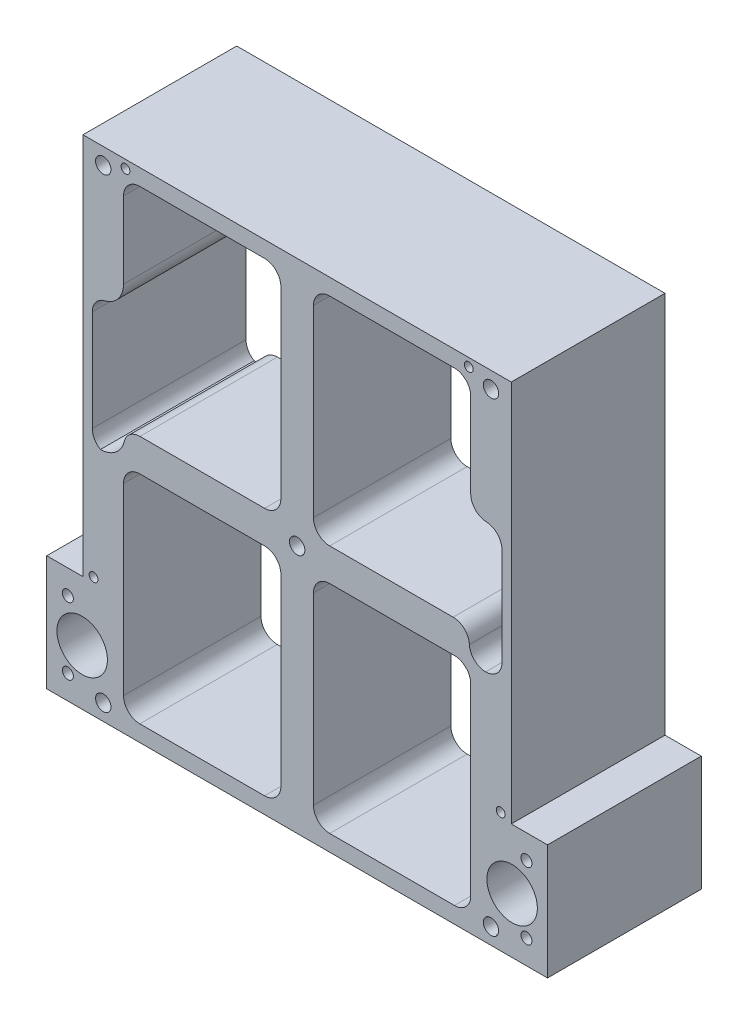
SolidWorks part; units mm, degrees
ref_plane "Front Plane" through (0, 0, 0) normal (0, 0, 1) x (1, 0, 0)
ref_plane "Top Plane" through (0, 0, 0) normal (0, 1, 0) x (1, 0, 0)
ref_plane "Right Plane" through (0, 0, 0) normal (1, 0, 0) x (0, 0, -1)
sketch "Sketch1" plane through (0, 0, 0) normal (0, 0, 1) x (1, 0, 0)
  line L0 (-85.5662, 44.958) -> (-97.6313, 44.958) construction
  line L1 (-97.6313, 44.958) -> (-97.6313, 0) construction
  line L2 (-97.6313, 0) -> (97.6313, 0) construction
  line L3 (97.6313, 0) -> (97.6312, 44.958) construction
  line L4 (97.6312, 44.958) -> (85.5663, 44.958) construction
  line L8 (83.5025, 45.5422) -> (83.5025, 194.183) construction
  line L9 (83.5025, 194.183) -> (-83.5025, 194.183) construction
  line L10 (-83.5025, 194.183) -> (-83.5025, 45.5422) construction
  line L14 (-83.5025, 44.958) -> (-97.6313, 44.958)
  line L15 (-97.6313, 44.958) -> (-97.6313, 0)
  line L16 (-97.6313, 0) -> (97.6313, 0)
  line L17 (97.6313, 0) -> (97.6312, 44.958)
  line L18 (97.6312, 44.958) -> (83.5025, 44.958)
  line L22 (83.5025, 44.958) -> (83.5025, 194.183)
  line L23 (83.5025, 194.183) -> (-83.5025, 194.183)
  line L24 (-83.5025, 194.183) -> (-83.5025, 44.958)
extrude "Boss-Extrude1" add sketch "Sketch1" against normal blind 59.944
sketch "Sketch2" plane through (0, 0, -59.944) normal (0, 0, -1) x (-1, 0, 0)
  line L0 (-38.54, -49.697) -> (-38.54, -49.707)
  line L1 (-38.54, -49.707) -> (74.04, -49.707)
  line L2 (74.04, -49.707) -> (74.04, 190.373)
  line L3 (74.04, 190.373) -> (-74.04, 190.373)
  line L4 (-74.04, 190.373) -> (-74.04, -49.707)
  line L5 (-74.04, -49.707) -> (-43.46, -49.707)
  line L6 (-43.46, -49.707) -> (-43.46, -49.697)
  line L7 (-43.46, -49.697) -> (-38.54, -49.697)
  line L8 (-36, -47.157) -> (-36, -47.167)
  line L9 (-36, -47.167) -> (71.5, -47.167)
  line L10 (71.5, -47.167) -> (71.5, 187.833)
  line L11 (71.5, 187.833) -> (-71.5, 187.833)
  line L12 (-71.5, 187.833) -> (-71.5, -47.167)
  line L13 (-71.5, -47.167) -> (-46, -47.167)
  line L14 (-46, -47.167) -> (-46, -47.157)
  line L15 (-46, -47.157) -> (-36, -47.157)
  line L16 (-36, -47.157) -> (-36, -47.167) construction
  line L17 (-36, -47.167) -> (71.5, -47.167) construction
  line L18 (71.5, -47.167) -> (71.5, 187.833) construction
  line L19 (71.5, 187.833) -> (-71.5, 187.833) construction
  line L20 (-71.5, 187.833) -> (-71.5, -47.167) construction
  line L21 (-71.5, -47.167) -> (-46, -47.167) construction
  line L22 (-46, -47.167) -> (-46, -47.157) construction
  line L23 (-46, -47.157) -> (-36, -47.157) construction
  dimension "D1" = 0
  dimension "D2" = 2.54
extrude "Cut-Extrude1" cut sketch "Sketch2" against normal blind 6.35
sketch "Sketch3" plane through (0, 0, -59.944) normal (0, 0, -1) x (-1, 0, 0)
  line L0 (-71.49, 45.353) -> (-71.49, 83.653) construction
  line L1 (-71.5, 64.5639) -> (-78.8025, 64.5639) construction
  line L2 (-71.5, 187.833) -> (-71.5, -47.167) construction
  line L3 (-74.04, 190.373) -> (-74.04, 0) construction
  line L4 (-71.5, 86.1539) -> (-78.8025, 86.1539)
  line L5 (-71.5, 42.9739) -> (-78.8025, 42.9739)
  line L6 (-71.5, 86.1539) -> (-71.5, 42.9739)
  line L7 (-78.8025, 86.1539) -> (-78.8025, 42.9739)
  dimension "D1" = 4.7625
  dimension "D2" = 21.59
  dimension "D3" = 21.59
extrude "Cut-Extrude2" cut sketch "Sketch3" against normal up to surface (6.35 mm away) up to face at (0, 95.1865, -53.594)
sketch "Sketch4" plane through (0, 0, -59.944) normal (0, 0, -1) x (-1, 0, 0)
  arc A0 (93.4715, 23.5197) -> (93.4715, 19.6603) centre (83.82, 21.59) ccw construction
  arc A1 (-74.1685, 23.5197) -> (-74.1685, 19.6603) centre (-83.82, 21.59) ccw construction
  circle A2 centre (83.82, 21.59) radius 9.8425
  circle A3 centre (-83.82, 21.59) radius 9.8425
extrude "Cut-Extrude3" cut sketch "Sketch4" against normal through all
hole_wizard "Hole1" positions "Sketch6" profile "Sketch5" legacy
sketch "Sketch6" plane through (0, 0, -59.944) normal (0, 0, -1) x (-1, 0, 0)
  line L0 (-97.6313, 22.479) -> (97.6313, 22.479) construction
  line L4 (-97.6313, 0) -> (-97.6312, 44.958) construction
  line L5 (97.6313, 44.958) -> (97.6313, 0) construction
  point P0 (-89.408, 35.56)
  point P3 (89.408, 35.56)
  point P16 (-89.408, 9.398)
  point P17 (89.408, 9.398)
sketch "Sketch5" plane through (89.408, 35.56, -59.944) normal (1, 0, 0) x (0, 1, 0)
  line L0 (0, 0) -> (0, 3.81)
  line L1 (0, 3.81) -> (2.5273, 3.81)
  line L2 (2.5273, 3.81) -> (2.6543, 0)
  line L3 (2.6543, 0) -> (0, 0)
  line L4 (0, 110) -> (0, -10) construction
  dimension "Minor Diameter" = 5.0546
  dimension "Depth" = 3.81
  dimension "Major Diameter" = 5.3086
hole_wizard "#6 Clearance Hole1" positions "Sketch8" profile "Sketch9" hole size "#6" standard "ANSI Inch" end condition through all
sketch "Sketch8" plane through (0, 0, -59.944) normal (0, 0, -1) x (-1, 0, 0)
  line L0 (-97.6312, 22.479) -> (97.6313, 22.479) construction
  line L1 (-97.6313, 0) -> (-97.6312, 44.958) construction
  line L2 (97.6313, 44.958) -> (97.6313, 0) construction
  point P0 (-89.408, 35.56)
  point P3 (89.408, 35.56)
  point P13 (89.408, 9.398)
  point P14 (-89.408, 9.398)
sketch "Sketch9" plane through (89.408, 35.56, -59.944) normal (1, 0, 0) x (0, 1, 0)
  line L0 (0, 0) -> (0, 59.944)
  line L1 (0, 59.944) -> (2.1526, 59.944)
  line L2 (2.1526, 59.944) -> (2.1526, 0)
  line L5 (2.1526, 0) -> (0, 0)
  line L11 (0, -6.35) -> (0, 107.95) construction
  dimension "Thru Hole Dia." = 4.3053
  dimension "Thru Hole Depth" = 59.944
sketch "Sketch10" plane through (0, 0, -59.944) normal (0, 0, -1) x (-1, 0, 0)
  circle A0 centre (-79.375, 46.863) radius 3.175
  circle A1 centre (-66.929, 191.008) radius 3.175
  circle A2 centre (66.929, 191.008) radius 3.175
  circle A3 centre (79.375, 46.863) radius 3.175
  dimension "D1" = 6.35
extrude "Boss-Extrude2" add sketch "Sketch10" against normal up to next (59.944 mm away)
hole_wizard "Hole2" positions "Sketch12" profile "Sketch11" legacy
sketch "Sketch12" plane through (0, 0, -59.944) normal (0, 0, -1) x (-1, 0, 0)
  point P0 (66.929, 191.008)
  point P2 (-66.929, 191.008)
  point P4 (-79.375, 46.863)
  point P6 (79.375, 46.863)
sketch "Sketch11" plane through (-66.929, 191.008, -59.944) normal (1, 0, 0) x (0, 1, 0)
  line L0 (0, 0) -> (0, 3.429)
  line L1 (0, 3.429) -> (1.9431, 3.429)
  line L2 (1.9431, 3.429) -> (2.0701, 0)
  line L3 (2.0701, 0) -> (0, 0)
  line L4 (0, 110) -> (0, -10) construction
  dimension "Minor Diameter" = 3.8862
  dimension "Depth" = 3.429
  dimension "Major Diameter" = 4.1402
hole_wizard "#4 Clearance Hole1" positions "Sketch14" profile "Sketch13" hole size "#4" standard "ANSI Inch" end condition through all
sketch "Sketch14" plane through (0, 0, -56.515) normal (0, 0, -1) x (-1, 0, 0)
  point P0 (79.375, 46.863)
  point P2 (-79.375, 46.863)
  point P5 (-66.929, 191.008)
  point P7 (66.929, 191.008)
sketch "Sketch13" plane through (-79.375, 46.863, -56.515) normal (1, 0, 0) x (0, 1, 0)
  line L0 (0, 0) -> (0, 56.515)
  line L1 (0, 56.515) -> (1.7272, 56.515)
  line L2 (1.7272, 56.515) -> (1.7272, 0)
  line L5 (1.7272, 0) -> (0, 0)
  line L11 (0, -6.35) -> (0, 107.95) construction
  dimension "Thru Hole Dia." = 3.4544
  dimension "Thru Hole Depth" = 56.515
sketch "Sketch15" plane through (0, 0, -59.944) normal (0, 0, -1) x (-1, 0, 0)
  line L0 (-74.04, 20.4826) -> (-74.04, 0) construction
  line L1 (-83.82, 31.4325) -> (-74.04, 31.4325)
  line L2 (-83.82, 31.4325) -> (-83.82, 11.7475)
  line L3 (-83.82, 11.7475) -> (-74.04, 11.7475)
  line L4 (-74.04, 31.4325) -> (-74.04, 11.7475)
  line L5 (74.04, 190.373) -> (74.04, 22.6974) construction
  line L6 (83.82, 11.7475) -> (74.04, 11.7475)
  line L7 (83.82, 11.7475) -> (83.82, 31.4325)
  line L8 (83.82, 31.4325) -> (74.04, 31.4325)
  line L9 (74.04, 11.7475) -> (74.04, 31.4325)
  arc A0 (-74.04, 22.6974) -> (-74.04, 20.4826) centre (-83.82, 21.59) ccw construction
  arc A1 (74.04, 20.4826) -> (74.04, 22.6974) centre (83.82, 21.59) ccw construction
  point P0 (-83.82, 21.59)
  point P11 (83.82, 21.59)
extrude "Cut-Extrude4" cut sketch "Sketch15" against normal up to surface (6.35 mm away) up to face at (25.5938, 87.5277, -53.594)
chamfer "Chamfer1" distance 2.54 angle 45 4 edges at (-74.04, 11.7475, -56.769) (-74.04, 31.4325, -56.769) (74.04, 11.7475, -56.769) (74.04, 31.4325, -56.769)
sketch "Sketch16" plane through (0, 0, -53.594) normal (0, 0, -1) x (-1, 0, 0)
  line L0 (0, 194.183) -> (0, 0) construction
  line L1 (-83.5025, 194.183) -> (83.5025, 194.183) construction
  line L2 (-74.04, 0) -> (74.04, 0) construction
  line L3 (0, 97.0915) -> (74.04, 97.0915) construction
  line L4 (74.04, 190.373) -> (74.04, 33.9725) construction
  line L5 (74.04, 97.0915) -> (74.04, 0) construction
  line L6 (74.04, 0) -> (0, 0) construction
  line L7 (0, 97.0915) -> (0, 0) construction
  line L8 (6.35, 90.7415) -> (67.69, 90.7415)
  line L9 (67.69, 90.7415) -> (67.69, 6.35)
  line L10 (67.69, 6.35) -> (6.35, 6.35)
  line L11 (6.35, 90.7415) -> (6.35, 6.35)
  line L12 (6.35, 103.4415) -> (6.35, 187.833)
  line L13 (67.69, 187.833) -> (6.35, 187.833)
  line L14 (67.69, 103.4415) -> (67.69, 187.833)
  line L15 (6.35, 103.4415) -> (67.69, 103.4415)
  line L16 (-6.35, 103.4415) -> (-67.69, 103.4415)
  line L17 (-67.69, 103.4415) -> (-67.69, 187.833)
  line L18 (-67.69, 187.833) -> (-6.35, 187.833)
  line L19 (-6.35, 103.4415) -> (-6.35, 187.833)
  line L20 (-6.35, 90.7415) -> (-6.35, 6.35)
  line L21 (-67.69, 6.35) -> (-6.35, 6.35)
  line L22 (-67.69, 90.7415) -> (-67.69, 6.35)
  line L23 (-6.35, 90.7415) -> (-67.69, 90.7415)
  dimension "D1" = 6.35
extrude "Cut-Extrude5" cut sketch "Sketch16" against normal through all
fillet "Fillet1" radius 6.35 16 edges at (6.35, 6.35, -26.797) (6.35, 90.7415, -26.797) (67.69, 90.7415, -26.797) (67.69, 6.35, -26.797) (-6.35, 6.35, -26.797) (-6.35, 90.7415, -26.797) (-67.69, 90.7415, -26.797) (-67.69, 6.35, -26.797) (-67.69, 103.4415, -26.797) (-67.69, 187.833, -26.797) (-6.35, 187.833, -26.797) (-6.35, 103.4415, -26.797) (67.69, 103.4415, -26.797) (6.35, 103.4415, -26.797) (6.35, 187.833, -26.797) (67.69, 187.833, -26.797)
hole_wizard "Hole3" positions "Sketch20" profile "Sketch19" legacy
sketch "Sketch20" plane through (0, 0, 0) normal (0, 0, 1) x (1, 0, 0)
  line L0 (-8.2099, 88.8816) -> (8.2099, 105.3014) construction
  line L3 (75.5963, 6.35) -> (-75.5962, 6.35)
  line L4 (75.5963, 6.35) -> (75.5963, 187.833)
  line L5 (75.5963, 187.833) -> (-75.5962, 187.833)
  line L6 (-75.5962, 6.35) -> (-75.5962, 187.833)
  line L7 (75.5963, 6.35) -> (-75.5962, 187.833) construction
  line L8 (75.5963, 187.833) -> (-75.5962, 6.35) construction
  line L15 (-67.69, 145.6373) -> (-83.5025, 145.6373) construction
  line L16 (-67.69, 109.7915) -> (-67.69, 181.483) construction
  line L17 (-83.5025, 194.183) -> (-83.5025, 44.958) construction
  line L18 (-61.34, 187.833) -> (-12.7, 187.833) construction
  arc A0 (-6.35, 84.3915) -> (-12.7, 90.7415) centre (-12.7, 84.3915) ccw construction
  arc A1 (6.35, 109.7915) -> (12.7, 103.4415) centre (12.7, 109.7915) ccw construction
  point P10 (0, 97.0915)
  point P11 (-75.5962, 187.833)
  point P14 (75.5963, 6.35)
  point P15 (75.5963, 187.833)
  point P16 (-75.5962, 6.35)
  point P108 (-75.5962, 97.0915)
  point P109 (-75.5962, 145.6373)
sketch "Sketch19" plane through (0, 97.0915, 0) normal (1, 0, 0) x (0, -1, 0)
  line L0 (0, 0) -> (0, 4.699)
  line L1 (0, 4.699) -> (2.8702, 4.699)
  line L2 (2.8702, 4.699) -> (2.9972, 0)
  line L3 (2.9972, 0) -> (0, 0)
  line L4 (0, 110) -> (0, -10) construction
  dimension "Minor Diameter" = 5.7404
  dimension "Depth" = 4.699
  dimension "Major Diameter" = 5.9944
hole_wizard "#8 Clearance Hole1" positions "Sketch22" profile "Sketch21" hole size "#8" standard "ANSI Inch" end condition through all
sketch "Sketch22" plane through (0, 0, -4.699) normal (0, 0, 1) x (1, 0, 0)
  point P0 (-75.5962, 187.833)
  point P3 (75.5963, 187.833)
  point P6 (75.5963, 6.35)
  point P9 (-75.5962, 6.35)
sketch "Sketch21" plane through (-75.5962, 187.833, -4.699) normal (1, 0, 0) x (0, -1, 0)
  line L0 (0, 0) -> (0, 55.245)
  line L1 (0, 55.245) -> (2.4574, 55.245)
  line L2 (2.4574, 55.245) -> (2.4574, 0)
  line L5 (2.4574, 0) -> (0, 0)
  line L11 (0, -6.35) -> (0, 107.95) construction
  dimension "Thru Hole Dia." = 4.9149
  dimension "Thru Hole Depth" = 55.245
sketch "Sketch23" plane through (0, 0, -59.944) normal (0, 0, -1) x (-1, 0, 0)
  line L0 (-79.8735, 116.713) -> (-67.1735, 116.713) construction
  line L2 (-67.1735, 91.313) -> (-79.8735, 91.313)
  line L3 (-67.1735, 91.313) -> (-67.1735, 142.113)
  line L4 (-67.1735, 142.113) -> (-79.8735, 142.113)
  line L5 (-79.8735, 91.313) -> (-79.8735, 142.113)
  line L6 (-67.1735, 91.313) -> (-79.8735, 142.113) construction
  line L7 (-67.1735, 142.113) -> (-79.8735, 91.313) construction
  point P2 (-73.5235, 116.713)
  point P3 (-73.5235, 116.713)
  dimension "D1" = 50.8
  dimension "D2" = 12.7
extrude "Cut-Extrude6" cut sketch "Sketch23" against normal through all
fillet "Fillet2" radius 6.35 3 edges at (79.8735, 91.313, -29.972) (79.8735, 142.113, -29.972) (67.1735, 107.283, -26.797)
fillet "Fillet4" radius 6.35 2 edges at (67.69, 142.113, -26.797) (67.1735, 91.313, -26.797)
mirror "Mirror1" about plane through (0, 0, 0) normal (1, 0, 0) of "Cut-Extrude6"
fillet "Fillet5" radius 9.525 2 edges at (-67.69, 142.113, -26.797) (-67.1735, 91.313, -26.797)
fillet "Fillet6" radius 6.35 1 edges at (-67.1735, 107.283, -26.797)
fillet "Fillet7" radius 6.35 2 edges at (-79.8735, 91.313, -29.972) (-79.8735, 142.113, -29.972)
